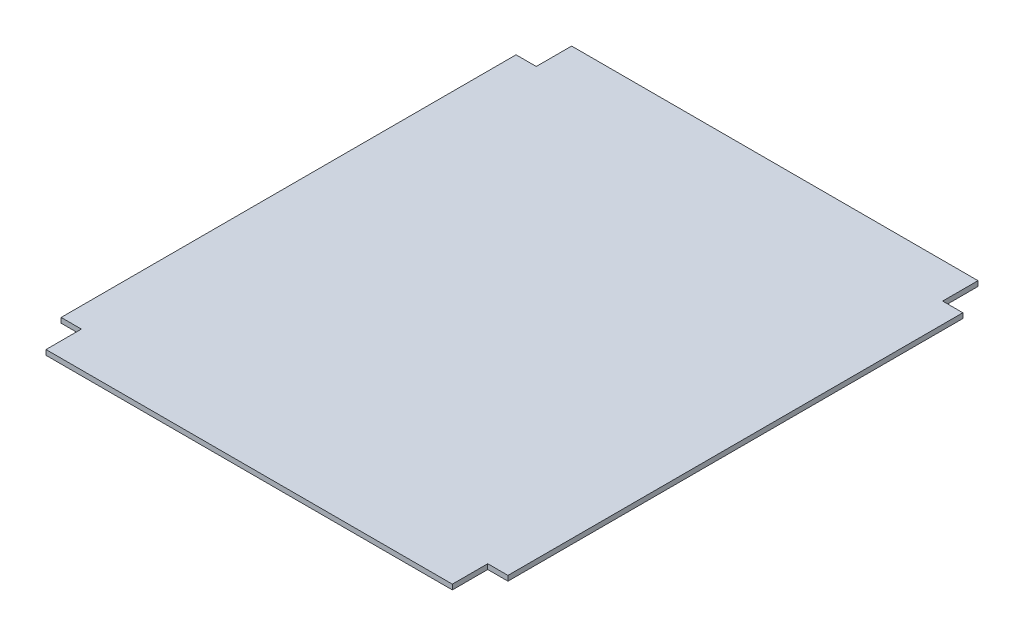
SolidWorks part; units mm, degrees
ref_plane "Front Plane" through (0, 0, 0) normal (0, 0, 1) x (1, 0, 0)
ref_plane "Top Plane" through (0, 0, 0) normal (0, 1, 0) x (1, 0, 0)
ref_plane "Right Plane" through (0, 0, 0) normal (1, 0, 0) x (0, 0, -1)
sketch "Sketch1" plane through (0, 0, 0) normal (0, 1, 0) x (1, 0, 0)
  line L0 (0, 0) -> (0, 3.5)
  line L1 (0, 3.5) -> (-2, 3.5)
  line L2 (-2, 3.5) -> (-2, 48.5)
  line L3 (-2, 48.5) -> (0, 48.5)
  line L4 (0, 48.5) -> (0, 52)
  line L5 (0, 52) -> (40.2, 52)
  line L6 (40.2, 52) -> (40.2, 48.5)
  line L7 (40.2, 48.5) -> (42.2, 48.5)
  line L8 (42.2, 48.5) -> (42.2, 3.5)
  line L9 (42.2, 3.5) -> (40.2, 3.5)
  line L10 (40.2, 3.5) -> (40.2, 0)
  line L11 (40.2, 0) -> (0, 0)
  dimension "D1" = 45
  dimension "D2" = 52
  dimension "D3" = 40.2
  dimension "D4" = 2
extrude "Boss-Extrude1" add sketch "Sketch1" along normal blind 0.5
